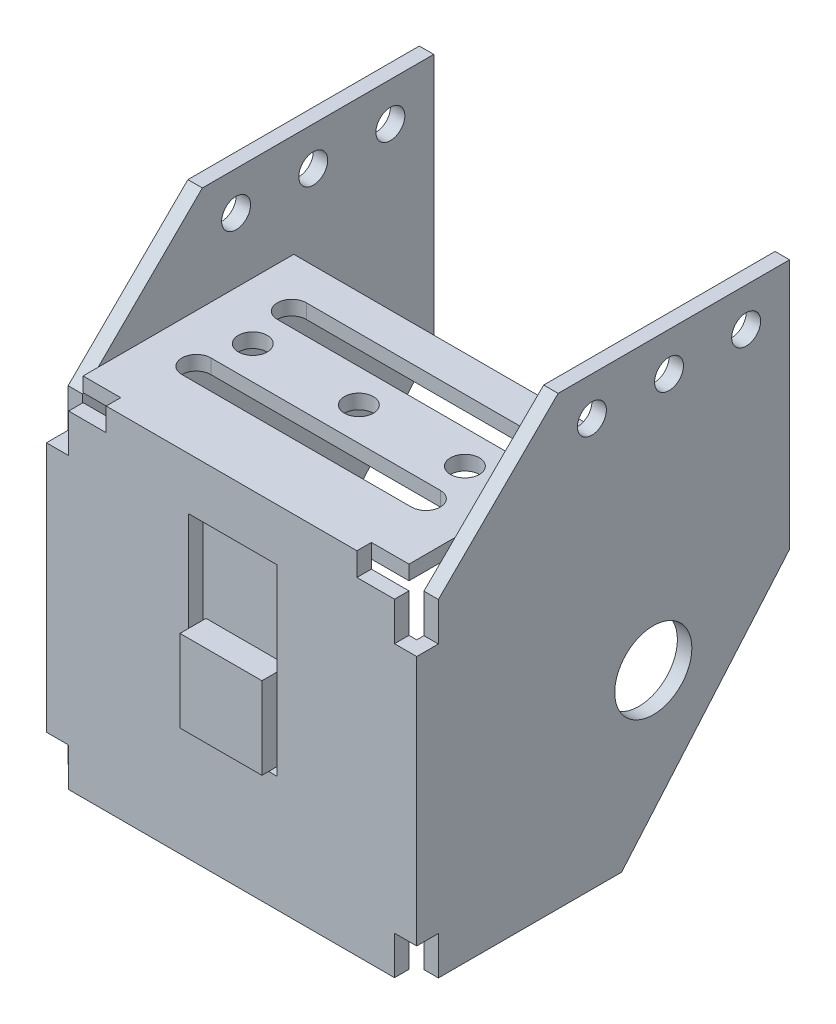
SolidWorks part; units mm, degrees
ref_plane "Front Plane" through (0, 0, 0) normal (0, 0, 1) x (1, 0, 0)
ref_plane "Top Plane" through (0, 0, 0) normal (0, 1, 0) x (1, 0, 0)
ref_plane "Right Plane" through (0, 0, 0) normal (1, 0, 0) x (0, 0, -1)
sketch "Sketch1" plane through (0, 0, 0) normal (0, 0, 1) x (1, 0, 0)
  line L0 (-16.9, 0) -> (16.9, 0)
  line L1 (-13, 34) -> (-13, 36.4)
  line L2 (55, 0) -> (-55, 0) construction
  line L3 (16.9, 0) -> (16.9, 4)
  line L4 (16.9, 4) -> (19.2, 4)
  line L5 (19.2, 4) -> (19.2, 30)
  line L6 (19.2, 30) -> (16.9, 30)
  line L7 (16.9, 30) -> (16.9, 34)
  line L8 (16.9, 34) -> (13, 34)
  line L9 (13, 34) -> (13, 36.4)
  line L10 (13, 36.4) -> (-13, 36.4)
  line L11 (0, -55) -> (0, 55) construction
  line L12 (-16.9, 34) -> (-13, 34)
  line L13 (-16.9, 30) -> (-16.9, 34)
  line L14 (-19.2, 30) -> (-16.9, 30)
  line L15 (-19.2, 4) -> (-19.2, 30)
  line L16 (-16.9, 4) -> (-19.2, 4)
  line L17 (-16.9, 0) -> (-16.9, 4)
  point P3 (10.5983, 34)
  point P4 (0, 0)
  point P18 (0, 36.4)
  point P25 (0, 0)
  dimension "D1" = 16.9
  dimension "D2" = 34
  dimension "D3" = 36.4
  dimension "D4" = 26
  dimension "D5" = 19.2
  dimension "D6" = 4
  dimension "D7" = 13
extrude "Boss-Extrude1" add sketch "Sketch1" along normal blind 1.5
sketch "Sketch3" plane through (0, 0, 1.5) normal (0, 0, 1) x (1, 0, 0)
  line L0 (0.825, 0) -> (-0.825, 0) construction
  line L1 (-4.45, 12) -> (4.7, 12)
  line L2 (-4.45, 12) -> (-4.45, 31)
  line L3 (-4.45, 31) -> (4.7, 31)
  line L4 (4.7, 12) -> (4.7, 31)
  line L5 (19.2, 4) -> (19.2, 30) construction
  point P4 (4.8996, 14.0748)
  dimension "D1" = 19
  dimension "D2" = 9.15
  dimension "D3" = 12
  dimension "D4" = 14.5
extrude "Cut-Extrude1" cut sketch "Sketch3" against normal up to surface (1.5 mm away) up to face at (0, 21.55, 0)
sketch "Sketch2" plane through (0, 0, 0) normal (0, 0, -1) x (-1, 0, 0)
  line L0 (16.9, 34) -> (16.9, 30) construction
  line L1 (-16.9, 36.4) -> (16.9, 36.4)
  line L2 (-16.9, 36.4) -> (-16.9, 34.9)
  line L3 (-16.9, 34.9) -> (16.9, 34.9)
  line L4 (16.9, 36.4) -> (16.9, 34.9)
  line L5 (-16.9, 30) -> (-16.9, 34) construction
  line L6 (-13, 36.4) -> (13, 36.4) construction
  dimension "D1" = 1.5
extrude "Boss-Extrude2" add sketch "Sketch2" along normal blind 21.85
sketch "Sketch4" plane through (0, 36.4, 0) normal (0, 1, 0) x (1, 0, 0)
  line L0 (-11.9, 6.75) -> (11.9, 6.75) construction
  line L1 (-11.9, 8.25) -> (11.9, 8.25)
  line L2 (-11.9, 5.25) -> (11.9, 5.25)
  line L3 (0, -12.8425) -> (0, 12.8425) construction
  line L4 (0, 15.15) -> (0, 8.25) construction
  line L5 (-16.9, 21.85) -> (16.9, 21.85) construction
  line L6 (-11.9, 16.65) -> (11.9, 16.65) construction
  line L7 (-11.9, 18.15) -> (11.9, 18.15)
  line L8 (-11.9, 15.15) -> (11.9, 15.15)
  arc A0 (-11.9, 8.25) -> (-11.9, 5.25) centre (-11.9, 6.75) ccw
  arc A1 (11.9, 5.25) -> (11.9, 8.25) centre (11.9, 6.75) ccw
  arc A2 (-11.9, 18.15) -> (-11.9, 15.15) centre (-11.9, 16.65) ccw
  arc A3 (11.9, 15.15) -> (11.9, 18.15) centre (11.9, 16.65) ccw
  circle A4 centre (-11, 11.7) radius 1.5
  circle A5 centre (0, 11.7) radius 1.5
  circle A6 centre (11, 11.7) radius 1.5
  point P2 (0, 6.75)
  point P13 (0, 16.65)
  point P26 (0, 11.7)
  point P27 (0, 0)
  dimension "D2" = 26.8
  dimension "D6" = 3
  dimension "D7" = 8
  dimension "D1" = 3
  dimension "D3" = 13.6
  dimension "D4" = 6.9
  dimension "D5" = 3
extrude "Cut-Extrude2" cut sketch "Sketch4" against normal up to surface (1.5 mm away) up to face at (0, 34.9, -7.2833)
sketch "Sketch5" plane through (19.2, 0, 0) normal (1, 0, 0) x (0, 0, -1)
  line L0 (0, 30) -> (0.75, 30)
  line L1 (0.75, 30) -> (0.75, 34)
  line L2 (0.75, 34) -> (13.17, 46.3)
  line L3 (13.17, 46.3) -> (37.17, 46.3)
  line L4 (37.17, 46.3) -> (37.17, 20.3)
  line L5 (37.17, 20.3) -> (19.75, 0)
  line L6 (19.75, 0) -> (0.75, 0)
  line L7 (0.75, 0) -> (0.75, 4)
  line L8 (0.75, 4) -> (0, 4)
  line L9 (-1.5, 4) -> (-1.5, 30) construction
  line L10 (21.12, 0) -> (-21.12, 0) construction
  line L15 (0, 4) -> (0, 30)
  line L16 (0, 30) -> (-1.5, 30)
  line L17 (-1.5, 30) -> (-1.5, 4)
  line L18 (-1.5, 4) -> (0, 4)
  line L20 (0, 30) -> (-1.5, 30)
  line L21 (-1.5, 30) -> (-1.5, 4)
  line L22 (-1.5, 4) -> (0, 4)
  point P16 (13.17, 46.3)
  point P17 (0.75, 33.8508)
  point P18 (37.17, 11.8792)
  point P19 (0.75, 33.3932)
  dimension "D1" = 2.25
  dimension "D2" = 36.42
  dimension "D3" = 46.3
  dimension "D4" = 24
  dimension "D5" = 19
  dimension "D6" = 26
  dimension "D7" = 4
  dimension "D8" = 0
extrude "Boss-Extrude3" add sketch "Sketch5" against normal blind 1.5
mirror "Mirror1" about plane through (0, 0, 0) normal (1, 0, 0) of "Boss-Extrude3"
sketch "Sketch6" plane through (19.2, 0, 0) normal (1, 0, 0) x (0, 0, -1)
  line L1 (37.17, 20.3) -> (37.17, 46.3) construction
  line L3 (37.17, 46.3) -> (13.17, 46.3) construction
  line L4 (19.75, 0) -> (37.17, 20.3) construction
  line L6 (0.75, 0) -> (19.75, 0) construction
  circle A0 centre (16.67, 42.3) radius 1.5
  circle A1 centre (24.67, 42.3) radius 1.5
  circle A2 centre (32.67, 42.3) radius 1.5
  circle A3 centre (23.0379, 16.5) radius 4
  dimension "D1" = 3
  dimension "D3" = 5
  dimension "D4" = 3
  dimension "D5" = 2.5
  dimension "D6" = 8
  dimension "D8" = 12.5
  dimension "D7" = 4.25
  dimension "D2" = 3
extrude "Cut-Extrude4" cut sketch "Sketch6" against normal up to surface (38.4 mm away) contours A0 | A1 | A2 region at (19.2, 42.3, -16.67) region at (19.2, 42.3, -24.67) region at (19.2, 42.3, -32.67) up to face at (-19.2, 21.49, -10.726)
extrude "Cut-Extrude5" cut sketch "Sketch6<3>" against normal up to surface (1.5 mm away) contours A3 region at (19.2, 16.5, -23.0379) up to face at (17.7, 42.3, -18.17)
sketch "Sketch6<3>" plane through (19.2, 0, 0) normal (1, 0, 0) x (0, 0, -1) same geometry as "Sketch6"
sketch "Sketch8" plane through (0, 0, 0) normal (0, 0, -1) x (-1, 0, 0)
  line L0 (21.12, 0) -> (-21.12, 0) construction
  line L1 (-12.7, 8.5) -> (11.3, 8.5)
  line L2 (-12.7, 8.5) -> (-12.7, 31.5)
  line L3 (-12.7, 31.5) -> (11.3, 31.5)
  line L4 (11.3, 8.5) -> (11.3, 31.5)
  line L5 (-17.7, 4) -> (-17.7, 30) construction
  dimension "D1" = 23
  dimension "D2" = 24
  dimension "D3" = 8.5
  dimension "D4" = 5
extrude "Boss-Extrude5" add sketch "Sketch8" along normal blind 1.5
sketch "Sketch9" plane through (0, 0, 0) normal (0, 0, 1) x (1, 0, 0)
  line L0 (-4.45, 12) -> (4.7, 12) construction
  line L1 (-4.1527, 12.5) -> (4.3473, 12.5)
  line L2 (-4.1527, 12.5) -> (-4.1527, 21)
  line L3 (-4.1527, 21) -> (4.3473, 21)
  line L4 (4.3473, 12.5) -> (4.3473, 21)
  line L5 (-4.45, 31) -> (-4.45, 12) construction
  point P4 (-4.1527, 13.0419)
  dimension "D1" = 8.5
  dimension "D2" = 0.5
  dimension "D3" = 0.2973
extrude "Boss-Extrude6" add sketch "Sketch9" along normal offset from surface (2.7 mm away) 1.2 up to face at (0, 21.55, 1.5) offset beyond the face yes
